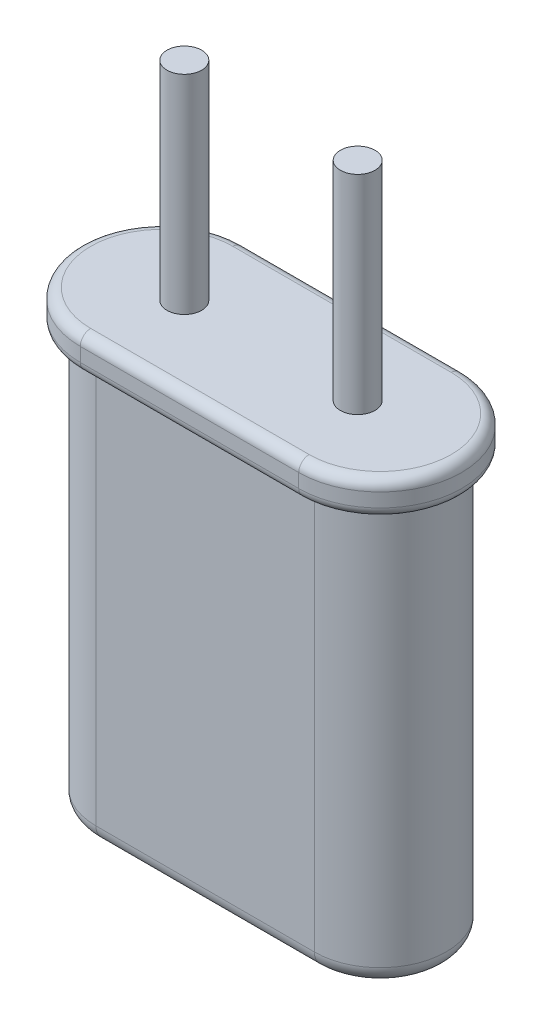
SolidWorks part; units mm, degrees
material "ABS PC"
ref_plane "Front Plane" through (0, 0, 0) normal (0, 0, 1) x (1, 0, 0)
ref_plane "Top Plane" through (0, 0, 0) normal (0, 1, 0) x (1, 0, 0)
ref_plane "Right Plane" through (0, 0, 0) normal (1, 0, 0) x (0, 0, -1)
sketch "Sketch1" plane through (0, 0, 0) normal (0, 1, 0) x (-1, 0, 0)
  line L0 (3.15, -2.35) -> (-3.15, -2.35)
  line L1 (3.15, 2.35) -> (-3.15, 2.35)
  line L2 (0, 2.35) -> (0, 0) construction
  line L3 (-5.5, 0) -> (0, 0) construction
  arc A0 (-3.15, 2.35) -> (-3.15, -2.35) centre (-3.15, 0) ccw
  arc A1 (3.15, 2.35) -> (3.15, -2.35) centre (3.15, 0) cw
  point P7 (0, -2.35)
  dimension "D2" = 2.35
  dimension "D3" = 3.15
extrude "Extrude1" add sketch "Sketch1" against normal blind 1
sketch "Sketch2" plane through (0, -1, 0) normal (0, -1, 0) x (1, 0, 0)
  line L4 (-3.15, -1.9) -> (3.15, -1.9)
  line L5 (3.15, 1.9) -> (-3.15, 1.9)
  line L8 (-3.15, -1.9) -> (3.15, -1.9)
  line L9 (3.15, 1.9) -> (-3.15, 1.9)
  arc A4 (3.15, -1.9) -> (3.15, 1.9) centre (3.15, 0) ccw
  arc A7 (-3.15, 1.9) -> (-3.15, -1.9) centre (-3.15, 0) ccw
  arc A8 (3.15, -1.9) -> (3.15, 1.9) centre (3.15, 0) ccw
  arc A9 (-3.15, 1.9) -> (-3.15, -1.9) centre (-3.15, 0) ccw
  point P16 (0, 0)
  dimension "D1" = 0.45
extrude "Extrude2" add sketch "Sketch2" along normal blind 12
fillet "Fillet1" radius 0.3 8 edges at (-5.5, 0, 0) (0, 0, 2.35) (5.5, 0, 0) (5.5, -1, 0) (-5.5, -1, 0) (0, -1, 2.35) (0, 0, -2.35) (0, -1, -2.35) tangent propagation no
fillet "Fillet2" radius 0.5 4 edges at (0, -13, -1.9) (-5.05, -13, 0) (0, -13, 1.9) (5.05, -13, 0) tangent propagation no
sketch "Sketch3" plane through (0, 0, 0) normal (0, 1, 0) x (-1, 0, 0)
  line L0 (0, 2.5207) -> (0, -2.7663) construction
  circle A0 centre (2.5, 0) radius 0.5
  circle A1 centre (-2.5, 0) radius 0.5
  point P5 (0, 0)
  dimension "D1" = 1
  dimension "D2" = 2.5
extrude "Extrude3" add sketch "Sketch3" along normal blind 6
